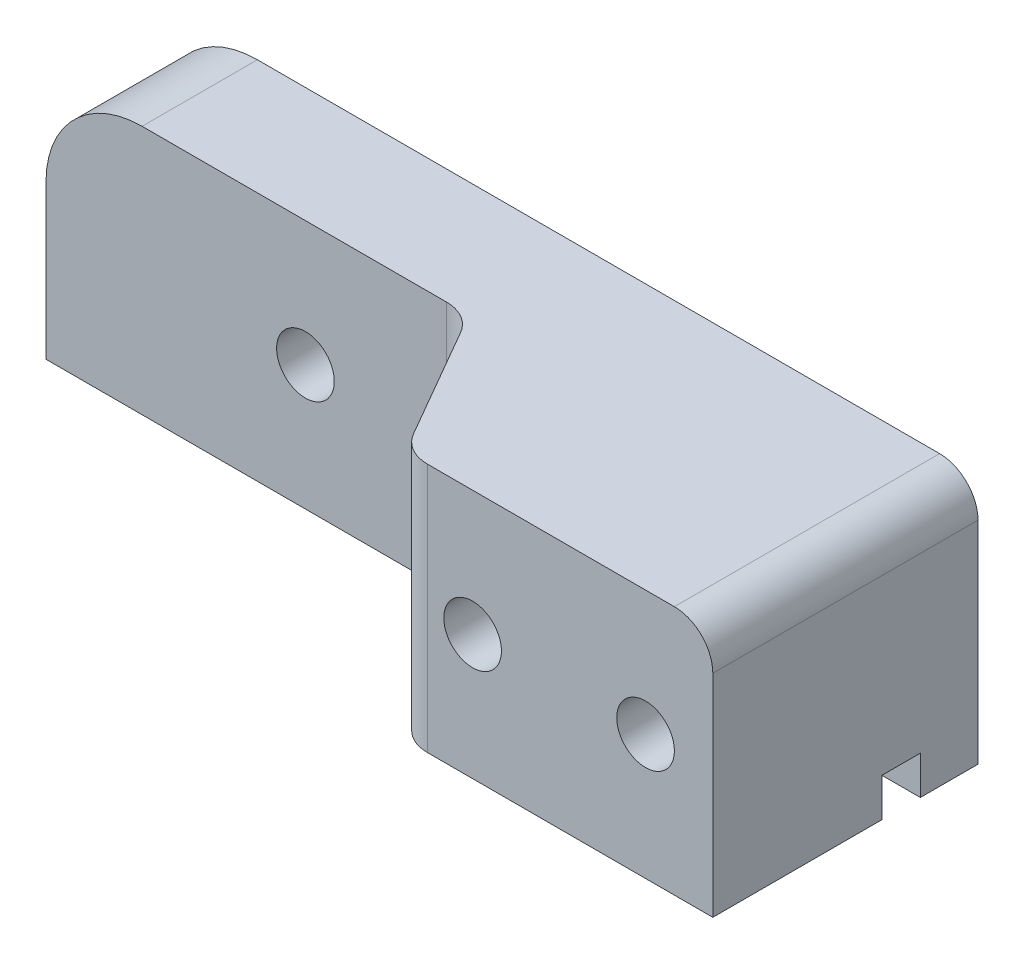
SolidWorks part; units mm, degrees
material "ABS"
ref_plane "Front" through (0, 0, 0) normal (0, 0, 1) x (1, 0, 0)
ref_plane "Top" through (0, 0, 0) normal (0, 1, 0) x (1, 0, 0)
ref_plane "Right" through (0, 0, 0) normal (1, 0, 0) x (0, 0, -1)
sketch "Esquisse1" plane through (0, 0, 0) normal (0, 0, 1) x (1, 0, 0)
  line L1 (0, 0) -> (42.5, 0)
  line L2 (0, 0) -> (0, 13)
  line L3 (0, 13) -> (42.5, 13)
  line L4 (42.5, 0) -> (42.5, 13)
  dimension "D1" = 13
  dimension "D2" = 42.5
extrude "Boss.-Extru.1" add sketch "Esquisse1" along normal blind 6
sketch "Esquisse2" plane through (42.5, 0, 0) normal (1, 0, 0) x (0, 0, -1)
  line L0 (-6, 0) -> (0, 0) construction
  line L1 (-5, 0) -> (-3, 0)
  line L2 (-5, 0) -> (-5, 2)
  line L3 (-5, 2) -> (-3, 2)
  line L4 (-3, 0) -> (-3, 2)
  line L5 (-6, 0) -> (-6, 13) construction
  dimension "D1" = 1
  dimension "D2" = 2
  dimension "D3" = 2
extrude "Enlèv. mat.-Extru.1" cut sketch "Esquisse2" against normal through all
sketch "Esquisse4" plane through (0, 0, 0) normal (0, -1, 0) x (1, 0, 0)
  line L0 (0, 3) -> (0, 0) construction
  line L1 (42.5, 6) -> (22, 6)
  line L2 (42.5, 6) -> (42.5, 13.8)
  line L3 (42.5, 13.8) -> (26.5, 13.8)
  line L4 (22, 6) -> (26.5, 13.8)
  dimension "D1" = 7.8
  dimension "D2" = 16
  dimension "D3" = 22
extrude "Boss.-Extru.2" add sketch "Esquisse4" against normal up to surface (13 mm away) up to face at (21.25, 13, 3)
sketch "Esquisse3" plane through (0, 0, 0) normal (0, 0, 1) x (1, 0, 0)
  line L0 (0, 13) -> (0, 0) construction
  line L1 (0, 0) -> (22, 0) construction
  line L2 (42.5, 13) -> (42.5, 0) construction
  circle A0 centre (13.5, 6.5) radius 1.5
  circle A1 centre (30, 6.5) radius 1.5
  circle A2 centre (39, 6.5) radius 1.5
  dimension "D1" = 9
  dimension "D2" = 16.5
  dimension "D3" = 13.5
  dimension "D4" = 6.5
  dimension "D5" = 3
  dimension "D6" = 3.5
extrude "Enlèv. mat.-Extru.2" cut sketch "Esquisse3" along normal through all
fillet "Congé1" radius 5 1 edges at (0, 13, 3)
sketch "Esquisse5" plane through (0, 0, 0) normal (0, 0, -1) x (-1, 0, 0)
  line L1 (-13.5, 9.6754) -> (-16.25, 8.0877)
  line L2 (-16.25, 8.0877) -> (-16.25, 4.9123)
  line L3 (-16.25, 4.9123) -> (-13.5, 3.3246)
  line L4 (-13.5, 3.3246) -> (-10.75, 4.9123)
  line L5 (-10.75, 4.9123) -> (-10.75, 8.0877)
  line L6 (-10.75, 8.0877) -> (-13.5, 9.6754)
  circle A0 centre (-13.5, 6.5) radius 2.75 construction
  circle A1 centre (-30, 6.5) radius 3
  circle A2 centre (-39, 6.5) radius 3
  dimension "D1" = 5.5
  dimension "D2" = 6
extrude "Enlèv. mat.-Extru.3" cut sketch "Esquisse5" against normal blind 3
fillet "Congé2" radius 2 3 edges at (42.5, 13, 6.9) (26.5, 6.5, 13.8) (22, 6.5, 6)
sketch "Esquisse6" plane through (0, 0, 0) normal (0, 0, -1) x (-1, 0, 0)
  line L0 (-27.5, -14.5) -> (-23.5, -14.5) construction
  line L1 (-27.5, 2) -> (-23.5, 2)
  line L2 (-27.5, -31) -> (-23.5, -31)
  arc A0 (-27.5, 2) -> (-27.5, -31) centre (-27.5, -14.5) ccw
  arc A1 (-23.5, -31) -> (-23.5, 2) centre (-23.5, -14.5) ccw
  circle A2 centre (-13.5, 6.5) radius 1.5 construction
  point P2 (-25.5, -14.5)
  dimension "D1" = 12
  dimension "D2" = 21
  dimension "D3" = 33
  dimension "D4" = 4
extrude "Enlèv. mat.-Extru.4" cut sketch "Esquisse6" against normal up to surface (5 mm away) up to face at (21.25, 1, 5)
